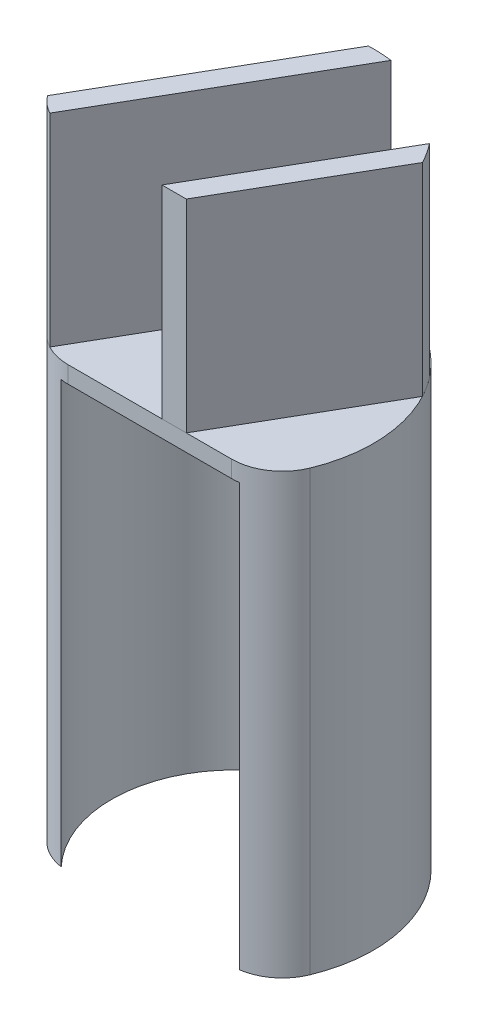
SolidWorks part; units mm, degrees
ref_plane "前视基准面" through (0, 0, 0) normal (0, 0, 1) x (1, 0, 0)
ref_plane "上视基准面" through (0, 0, 0) normal (0, 1, 0) x (1, 0, 0)
ref_plane "右视基准面" through (0, 0, 0) normal (1, 0, 0) x (0, 0, -1)
other "Configuration Table"
sketch "草图1" plane through (0, 0, 0) normal (0, 1, 0) x (1, 0, 0)
  circle A0 centre (0, 0) radius 14.5
  circle A1 centre (0, 0) radius 16.5
  dimension "D1" = 29
  dimension "D2" = 2
extrude "凸台-拉伸1" add sketch "草图1" along normal blind 35
sketch "草图3" plane through (0, 35, 0) normal (0, 1, 0) x (1, 0, 0)
  circle A1 centre (0, 0) radius 16.5
  circle A2 centre (0, 0) radius 16.5
  dimension "D1" = 0
extrude "凸台-拉伸2" add sketch "草图3" along normal blind 2
ref_plane "基准面1" through (0, 0, 10) normal (0, 0, 1) x (1, 0, 0)
sketch "草图4" plane through (0, 0, 10) normal (0, 0, 1) x (1, 0, 0)
  line L1 (-21.3332, 39.7218) -> (28.4145, 39.7218)
  line L2 (-21.3332, 39.7218) -> (-21.3332, -3.9689)
  line L3 (-21.3332, -3.9689) -> (28.4145, -3.9689)
  line L4 (28.4145, 39.7218) -> (28.4145, -3.9689)
extrude "切除-拉伸1" cut sketch "草图4" along normal through all
sketch "草图5" plane through (0, 37, 0) normal (0, 1, 0) x (1, 0, 0)
  circle A0 centre (0, 0) radius 3.75
  dimension "D1" = 7.5
extrude "切除-拉伸2" cut sketch "草图5" against normal up to next
fillet "圆角1" radius 6 2 edges at (-13.1244, 18.5, 10) (13.1244, 18.5, 10)
sketch "草图6" plane through (0, 37, 0) normal (0, 1, 0) x (1, 0, 0)
  line L0 (13.0479, 10.0996) -> (1.4434, -10)
  line L1 (-0.5833, 16.4897) -> (-14.4988, -7.6126)
  line L2 (-24.0688, -10) -> (24.0688, -10) construction
  line L3 (2.2226, 16.3496) -> (-12.5707, -9.2732)
  line L4 (14.5721, 7.7397) -> (4.3301, -10)
  line L5 (-9.7082, -10) -> (9.7082, -10) construction
  line L7 (-9.7082, -10) -> (9.7082, -10)
  line L8 (1.4434, -10) -> (4.3301, -10)
  circle A0 centre (0, 0) radius 6.25 construction
  arc A1 (-15.2558, -6.2857) -> (-9.7082, -10) centre (-9.7082, -4) ccw construction
  arc A2 (15.2558, -6.2857) -> (-15.2558, -6.2857) centre (0, 0) ccw construction
  arc A3 (2.2226, 16.3496) -> (-0.5833, 16.4897) centre (0, 0) ccw
  arc A6 (15.2558, -6.2857) -> (-15.2558, -6.2857) centre (0, 0) ccw
  arc A7 (-15.2558, -6.2857) -> (-9.7082, -10) centre (-9.7082, -4) ccw
  arc A8 (9.7082, -10) -> (15.2558, -6.2857) centre (9.7082, -4) ccw
  arc A9 (14.5721, 7.7397) -> (13.0479, 10.0996) centre (0, 0) ccw
  arc A10 (-14.4988, -7.6126) -> (-12.5707, -9.2732) centre (-9.7082, -4) ccw
  dimension "D1" = 12.5
  dimension "D2" = 60
  dimension "D3" = 2.5
  dimension "D4" = 2.5
  dimension "D5" = 0
extrude "凸台-拉伸3" add sketch "草图6" along normal blind 24 separate body
sketch "草图7" plane through (0, 0, 0) normal (0, -1, 0) x (1, 0, 0)
  arc A4 (-10.5572, 9.9396) -> (10.5572, 9.9396) centre (0, 0) ccw
  arc A5 (-10.5572, 9.9396) -> (-15.2558, 6.2857) centre (-9.7082, 4) ccw
  arc A6 (-15.2558, 6.2857) -> (15.2558, 6.2857) centre (0, 0) ccw
  arc A7 (15.2558, 6.2857) -> (10.5572, 9.9396) centre (9.7082, 4) ccw
  arc A8 (-10.5572, 9.9396) -> (10.5572, 9.9396) centre (0, 0) ccw
  arc A9 (-10.5572, 9.9396) -> (-15.2558, 6.2857) centre (-9.7082, 4) ccw
  arc A10 (-15.2558, 6.2857) -> (15.2558, 6.2857) centre (0, 0) ccw
  arc A11 (15.2558, 6.2857) -> (10.5572, 9.9396) centre (9.7082, 4) ccw
  dimension "D1" = 0
extrude "凸台-拉伸4" add sketch "草图7" along normal blind 15
